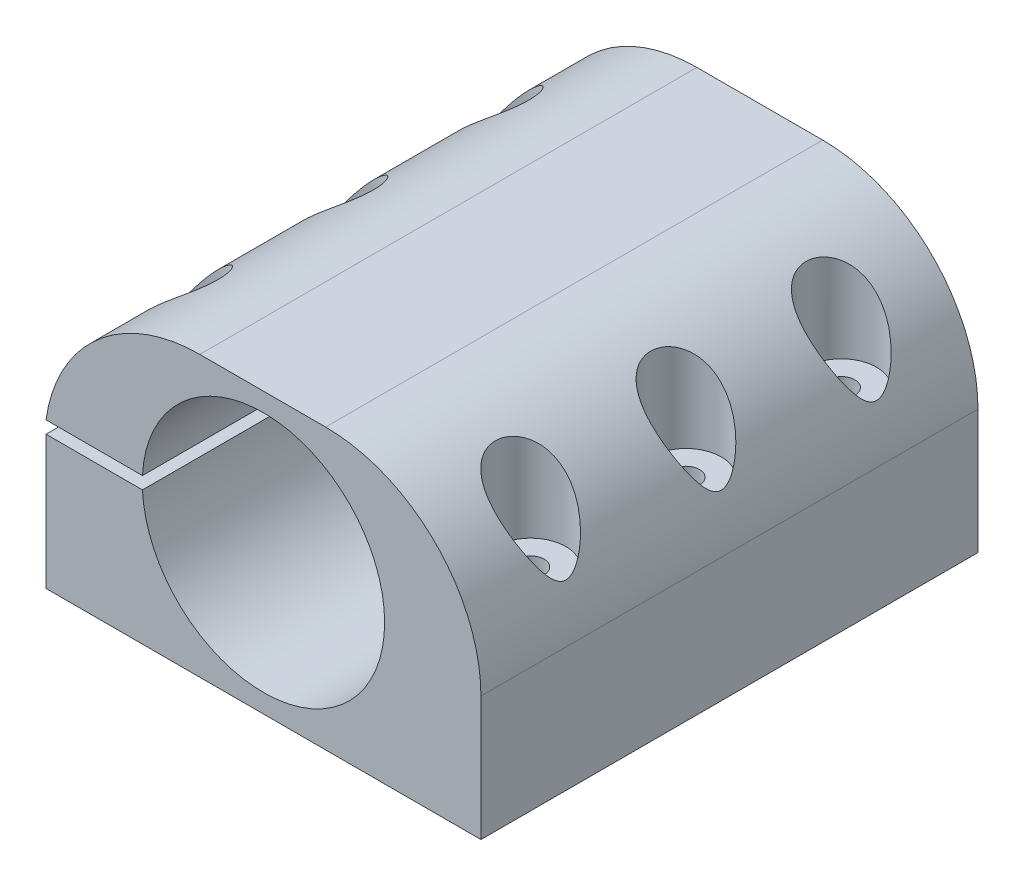
SolidWorks part; units mm, degrees
ref_plane "Front Plane" through (0, 0, 0) normal (0, 0, 1) x (1, 0, 0)
ref_plane "Top Plane" through (0, 0, 0) normal (0, 1, 0) x (1, 0, 0)
ref_plane "Right Plane" through (0, 0, 0) normal (1, 0, 0) x (0, 0, -1)
sketch "Sketch1" plane through (0, 0, 0) normal (0, 0, 1) x (1, 0, 0)
  line L0 (-19.4743, -1) -> (-35, -1)
  line L1 (-35, 22.5) -> (35, 22.5)
  line L2 (-35, 22.5) -> (-35, 1)
  line L3 (-35, -22.5) -> (35, -22.5)
  line L4 (35, 22.5) -> (35, -22.5)
  line L5 (-35, 22.5) -> (35, -22.5) construction
  line L6 (-35, -22.5) -> (35, 22.5) construction
  line L7 (55, 0) -> (-55, 0) construction
  line L8 (-19.4743, 1) -> (-35, 1)
  line L9 (-35, -1) -> (-35, -22.5)
  arc A0 (-19.4743, -1) -> (-19.4743, 1) centre (0, 0) ccw
  dimension "D1" = 39
  dimension "D2" = 45
  dimension "D3" = 70
  dimension "D4" = 1
extrude "Boss-Extrude1" add sketch "Sketch1" along normal blind 80
sketch "Sketch2" plane through (0, 22.5, 0) normal (0, 1, 0) x (1, 0, 0)
  line L0 (28, 0) -> (28, -80) construction
  line L1 (35, 0) -> (-35, 0) construction
  line L2 (35, -80) -> (-35, -80) construction
  line L3 (35, -80) -> (35, 0) construction
  circle A0 centre (28, -15) radius 2.175
  circle A1 centre (28, -40) radius 2.175
  circle A2 centre (28, -65) radius 2.175
  circle A3 centre (28, -65) radius 5.675
  circle A4 centre (28, -40) radius 5.675
  circle A5 centre (28, -15) radius 5.675
  point P8 (28, -15)
  point P9 (28, -65)
  point P10 (28, -40)
  dimension "D4" = 4.35
  dimension "D1" = 7
  dimension "D2" = 15
  dimension "D3" = 15
  dimension "D5" = 3.5
extrude "Cut-Extrude1" cut sketch "Sketch2" against normal through all contours L0 A2 | A2 L0 | A1 L0 | L0 A1 | A0 L0 | L0 A0 region at (28.9231, 22.5, 15) region at (27.0769, 22.5, 15) region at (28.9231, 22.5, 40) region at (27.0769, 22.5, 40) region at (28.9231, 22.5, 65) region at (27.0769, 22.5, 65)
extrude "Cut-Extrude2" cut sketch "Sketch2<3>" against normal blind 18
sketch "Sketch2<3>" plane through (0, 22.5, 0) normal (0, 1, 0) x (1, 0, 0) same geometry as "Sketch2"
mirror "Mirror1" about plane through (0, 0, 0) normal (1, 0, 0) of "Cut-Extrude1", "Cut-Extrude2"
chamfer "Chamfer2" [suppressed] distance 1 angle 45
sketch "Sketch3" plane through (0, 0, 80) normal (0, 0, 1) x (1, 0, 0)
  line L0 (-35, 1) -> (-19.4743, 1) construction
  line L1 (-33.4851, 1) -> (-35, 1)
  line L2 (-35, 1) -> (-35, 31)
  line L3 (-35, 31) -> (35, 31)
  line L5 (0, -55) -> (0, 55) construction
  line L7 (35, 1) -> (35, 31)
  line L8 (33.4851, 1) -> (35, 1)
  arc A5 (-33.4559, -1.7179) -> (-33.4559, 1.7179) centre (0, 0) ccw
  arc A6 (-33.4559, -1.7179) -> (-33.4851, 1) centre (0, 0) ccw
  point P13 (0, 31)
  line M3 (35, -22.5) -> (35, 22.5)
  line M4 (35, 22.5) -> (-35, 22.5)
  line M5 (-35, 22.5) -> (-35, 1)
  line M6 (-35, 1) -> (-19.4743, 1)
  dimension "D2" = 30
  dimension "D1" = 14
extrude "Cut-Extrude3" [suppressed] cut sketch "Sketch3" against normal through all contours A6 M4 M5 M6 | A6 L8 M3 M4
fillet "Fillet3" radius 25 2 edges at (-35, 22.5, 40) (35, 22.5, 40)
